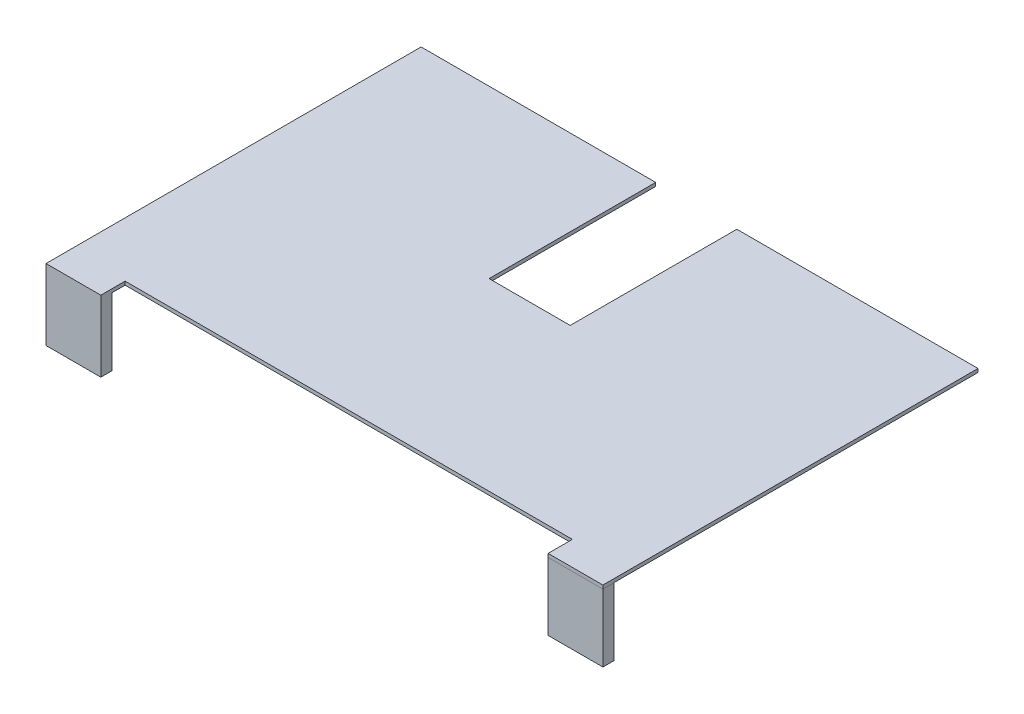
SolidWorks part; units mm, degrees
ref_plane "Front Plane" through (0, 0, 0) normal (0, 0, 1) x (1, 0, 0)
ref_plane "Top Plane" through (0, 0, 0) normal (0, 1, 0) x (1, 0, 0)
ref_plane "Right Plane" through (0, 0, 0) normal (1, 0, 0) x (0, 0, -1)
sketch "Sketch1" plane through (0, 0, 0) normal (0, 0, 1) x (1, 0, 0)
  line L0 (63.5, 27.8) -> (51, 27.8)
  line L1 (51, 27.8) -> (51, 12.4)
  line L2 (63.5, 12.4) -> (25, 12.4) construction
  line L3 (51, 12.4) -> (63.5, 12.4)
  line L4 (63.5, 12.4) -> (63.5, 27.8)
  line L5 (50.5, 23.51) -> (50.5, 14.7515) construction
  line L6 (-63.5, 12.4) -> (-63.5, 27.8)
  line L7 (-63.5, 27.8) -> (-51, 27.8)
  line L8 (-51, 27.8) -> (-51, 12.4)
  line L9 (-25, 12.4) -> (-63.5, 12.4) construction
  line L10 (-51, 12.4) -> (-63.5, 12.4)
  line L11 (-50.5, 23.51) -> (-50.5, 14.7515) construction
  dimension "D1" = 0.5
  dimension "D2" = 0.5
extrude "Boss-Extrude1" add sketch "Sketch1" against normal up to surface (2.54 mm away)
sketch "Sketch2" plane through (0, 27.8, 0) normal (0, 1, 0) x (1, 0, 0)
  line L0 (-63.5, 85.5459) -> (-63.5, 0)
  line L1 (-63.5, 85.5459) -> (63.5, 85.5459)
  line L2 (-63.5, 0) -> (-51, 0)
  line L3 (-51, 0) -> (-51, 2.54)
  line L4 (-51, 2.54) -> (-51, 5.54)
  line L5 (-51, 5.54) -> (51, 5.54)
  line L6 (51, 5.54) -> (51, 2.54)
  line L9 (63.5, 85.5459) -> (63.5, 0)
  line L10 (63.5, 0) -> (51, 0)
  line L11 (51, 0) -> (51, 2.54)
  dimension "D1" = 3
extrude "Boss-Extrude2" add sketch "Sketch2" along normal blind 0.8
sketch "Sketch3" plane through (0, 28.6, 0) normal (0, 1, 0) x (1, 0, 0)
  line L0 (0, 0) -> (0, 85.5459) construction
  line L1 (63.5, 85.5459) -> (-63.5, 85.5459) construction
  line L7 (-10, 85.5459) -> (-10, 55.762)
  line L8 (8.5, 85.5459) -> (8.5, 47.5459)
  line L9 (8.5, 47.5459) -> (-10, 47.5459)
  line L10 (-10, 47.5459) -> (-10, 55.762)
  line L11 (-10, 85.5459) -> (8.5, 85.5459)
  dimension "D1" = 10
  dimension "D2" = 8.5
  dimension "D3" = 38
extrude "Cut-Extrude1" cut sketch "Sketch3" against normal through all
